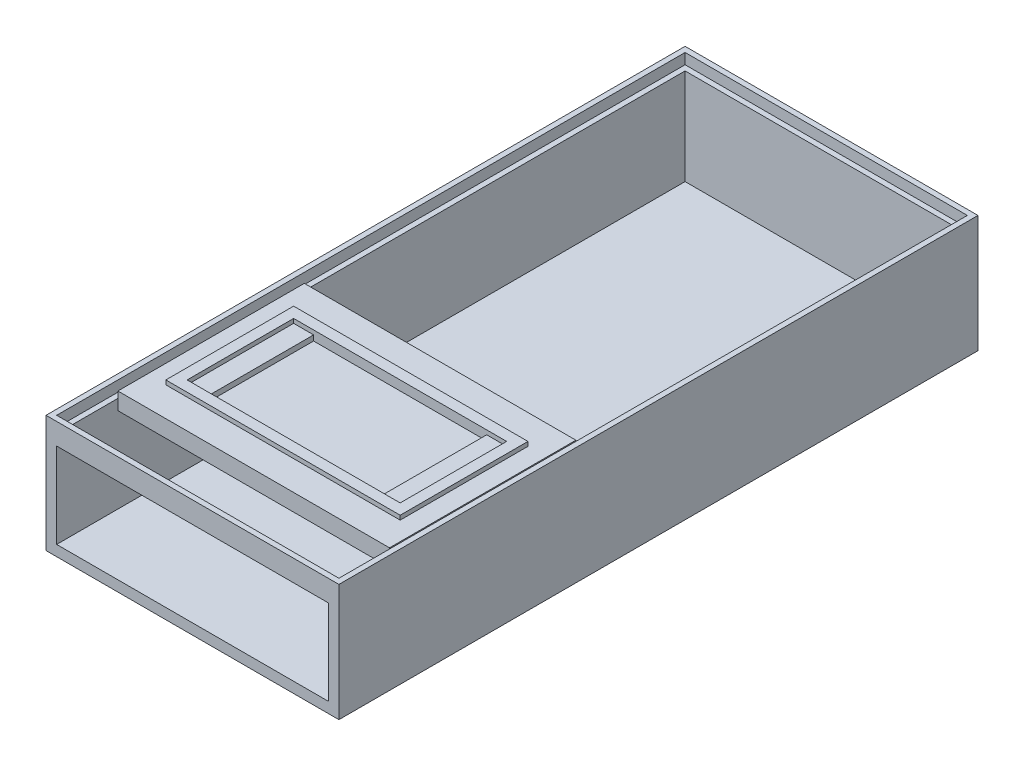
SolidWorks part; units mm, degrees
ref_plane "Front Plane" through (0, 0, 0) normal (0, 0, 1) x (1, 0, 0)
ref_plane "Top Plane" through (0, 0, 0) normal (0, 1, 0) x (1, 0, 0)
ref_plane "Right Plane" through (0, 0, 0) normal (1, 0, 0) x (0, 0, -1)
sketch "Sketch1" plane through (0, 0, 0) normal (0, 1, 0) x (1, 0, 0)
  line L1 (0, 0) -> (139.7, 0)
  line L2 (0, 0) -> (0, 304.8)
  line L3 (0, 304.8) -> (139.7, 304.8)
  line L4 (139.7, 0) -> (139.7, 304.8)
  dimension "D1" = 304.8
  dimension "D2" = 139.7
extrude "Boss-Extrude1" add sketch "Sketch1" along normal blind 5.08
sketch "Sketch2" plane through (0, 5.08, 0) normal (0, 1, 0) x (1, 0, 0)
  line L1 (0, 304.8) -> (139.7, 304.8)
  line L2 (0, 304.8) -> (0, 0)
  line L3 (0, 0) -> (139.7, 0)
  line L4 (139.7, 304.8) -> (139.7, 0)
  line L5 (5.08, 299.72) -> (134.62, 299.72)
  line L6 (5.08, 299.72) -> (5.08, 5.08)
  line L7 (5.08, 5.08) -> (134.62, 5.08)
  line L8 (134.62, 299.72) -> (134.62, 5.08)
  line M9 (0, 304.8) -> (0, 0)
  line M10 (0, 0) -> (139.7, 0)
  line M11 (139.7, 0) -> (139.7, 304.8)
  line M12 (139.7, 304.8) -> (0, 304.8)
  dimension "D1" = 5.08
  dimension "D2" = 5.08
  dimension "D3" = 5.08
  dimension "D4" = 5.08
extrude "Walls" add sketch "Sketch2" along normal blind 50.8 contours L5 L8 L7 L6 M12 M9 M10 M11 region at (69.85, 5.08, -301.4471)
sketch "Sketch3" plane through (0, 55.88, 0) normal (0, 1, 0) x (1, 0, 0)
  line L1 (5.08, 299.72) -> (134.62, 299.72)
  line L2 (5.08, 299.72) -> (5.08, 5.08)
  line L3 (5.08, 5.08) -> (134.62, 5.08)
  line L4 (134.62, 299.72) -> (134.62, 5.08)
  line L5 (2.54, 302.26) -> (137.16, 302.26)
  line L6 (2.54, 302.26) -> (2.54, 2.54)
  line L7 (2.54, 2.54) -> (137.16, 2.54)
  line L8 (137.16, 302.26) -> (137.16, 2.54)
  line M13 (5.08, 299.72) -> (134.62, 299.72)
  line M14 (134.62, 299.72) -> (134.62, 5.08)
  line M15 (134.62, 5.08) -> (5.08, 5.08)
  line M16 (5.08, 5.08) -> (5.08, 299.72)
  dimension "D1" = 2.54
  dimension "D2" = 2.54
  dimension "D3" = 2.54
  dimension "D4" = 2.54
extrude "Cut-Extrude1" cut sketch "Sketch3" against normal blind 5.08 contours L8 L5 L6 L7 M16 M13 M14 M15 region at (69.85, 55.88, -301.9314)
sketch "Sketch5" plane through (0, 5.08, 0) normal (0, 1, 0) x (1, 0, 0)
  line L0 (5.08, 5.08) -> (5.08, 299.72) construction
  line L1 (5.08, 118.11) -> (134.62, 118.11)
  line L2 (5.08, 118.11) -> (5.08, 29.21)
  line L3 (5.08, 29.21) -> (134.62, 29.21)
  line L4 (134.62, 118.11) -> (134.62, 29.21)
  line L6 (134.62, 299.72) -> (134.62, 5.08) construction
  point P8 (134.62, 73.66)
  point P9 (0, 0)
  dimension "D1" = 73.66
  dimension "D2" = 88.9
extrude "Button Support" add sketch "Sketch5" along normal blind 48.768
sketch "Sketch6" plane through (0, 53.848, 0) normal (0, 1, 0) x (1, 0, 0)
  line L0 (0, 0) -> (139.7, 0) construction
  line L1 (19.05, 99.06) -> (120.65, 99.06)
  line L2 (19.05, 99.06) -> (19.05, 48.26)
  line L3 (19.05, 48.26) -> (120.65, 48.26)
  line L4 (120.65, 99.06) -> (120.65, 48.26)
  line L5 (125.73, 104.14) -> (13.97, 104.14)
  line L6 (125.73, 104.14) -> (125.73, 43.18)
  line L7 (125.73, 43.18) -> (13.97, 43.18)
  line L8 (13.97, 104.14) -> (13.97, 43.18)
  line L9 (134.62, 118.11) -> (5.08, 118.11) construction
  point P8 (69.85, 104.14)
  point P9 (69.85, 99.06)
  point P10 (120.65, 73.66)
  point P11 (125.73, 73.66)
  point P16 (69.85, 118.11)
  dimension "D1" = 50.8
  dimension "D2" = 73.66
  dimension "D3" = 101.6
  dimension "D4" = 5.08
  dimension "D5" = 5.08
extrude "Boss-Extrude4" add sketch "Sketch6" along normal blind 2.032
sketch "Sketch7" plane through (0, 53.848, 0) normal (0, 1, 0) x (1, 0, 0)
  line L0 (19.05, 48.26) -> (120.65, 48.26) construction
  line L1 (28.575, 48.26) -> (111.125, 48.26)
  line L2 (28.575, 48.26) -> (28.575, 99.06)
  line L3 (28.575, 99.06) -> (111.125, 99.06)
  line L4 (111.125, 48.26) -> (111.125, 99.06)
  line L5 (120.65, 99.06) -> (19.05, 99.06) construction
  point P8 (69.85, 99.06)
  point P9 (69.85, 48.26)
  dimension "D1" = 82.55
  dimension "D2" = 50.8
extrude "Cut-Extrude2" cut sketch "Sketch7" against normal blind 2.54
sketch "Sketch4" plane through (0, 0, 0) normal (0, 0, 1) x (1, 0, 0)
  line L0 (0, 0) -> (139.7, 0) construction
  line L1 (5.08, 45.72) -> (134.62, 45.72)
  line L2 (5.08, 45.72) -> (5.08, 5.08)
  line L3 (5.08, 5.08) -> (134.62, 5.08)
  line L4 (134.62, 45.72) -> (134.62, 5.08)
  line L5 (0, 55.88) -> (0, 0) construction
  line L6 (139.7, 55.88) -> (139.7, 0) construction
  line L7 (0, 55.88) -> (139.7, 55.88) construction
  dimension "D1" = 5.08
  dimension "D2" = 5.08
  dimension "D3" = 5.08
  dimension "D4" = 10.16
extrude "Cut-Extrude3" cut sketch "Sketch4" against normal blind 139.7
